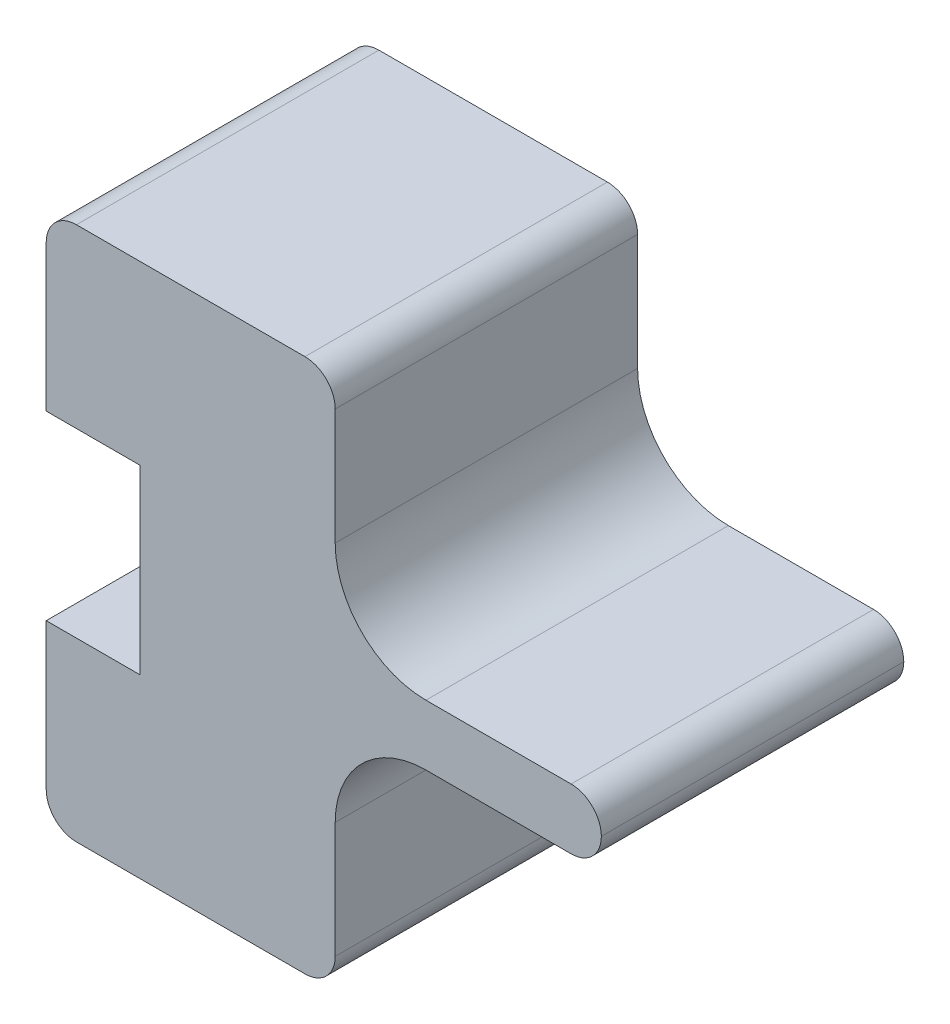
SolidWorks part; units mm, degrees
ref_plane "Plan de face" through (0, 0, 0) normal (0, 0, 1) x (1, 0, 0)
ref_plane "Plan de dessus" through (0, 0, 0) normal (0, 1, 0) x (1, 0, 0)
ref_plane "Plan de droite" through (0, 0, 0) normal (1, 0, 0) x (0, 0, -1)
sketch "Esquisse1" plane through (0, 0, 0) normal (0, 0, 1) x (1, 0, 0)
  line L0 (90, -10) -> (90, 10)
  line L1 (90, -58) -> (90, 58) construction
  line L2 (90, 10) -> (31.9949, 10)
  line L3 (1.9949, 40) -> (1.9949, 88.3751)
  line L4 (1.9949, 88.3751) -> (-83.5559, 88.3751)
  line L5 (-93.5559, 78.3751) -> (-93.5559, 30)
  line L6 (-93.5559, 30) -> (-22.5559, 30)
  line L7 (-22.5559, 30) -> (-22.5559, -30)
  line L8 (-73.7109, 0) -> (58.7084, 0) construction
  line L9 (-93.5559, -30) -> (-22.5559, -30)
  line L10 (-93.5559, -78.3751) -> (-93.5559, -30)
  line L11 (1.9949, -88.3751) -> (-83.5559, -88.3751)
  line L12 (1.9949, -40) -> (1.9949, -88.3751)
  line L13 (90, -10) -> (31.9949, -10)
  arc A0 (31.9949, 10) -> (1.9949, 40) centre (31.9949, 40) cw
  arc A1 (1.9949, -40) -> (31.9949, -10) centre (31.9949, -40) cw
  arc A2 (-93.5559, -78.3751) -> (-83.5559, -88.3751) centre (-83.5559, -78.3751) ccw
  arc A3 (-83.5559, 88.3751) -> (-93.5559, 78.3751) centre (-83.5559, 78.3751) ccw
  point P14 (-22.5559, 0)
  point P19 (90, 0)
  point P21 (1.9949, 10)
  point P24 (1.9949, -10)
  point P27 (-93.5559, -88.3751)
  point P30 (-93.5559, 88.3751)
  dimension "D6" = 30
  dimension "D7" = 30
  dimension "D8" = 10
  dimension "D1" = 30
  dimension "D2" = 71
  dimension "D3" = 22.5559
  dimension "D4" = 88.3751
  dimension "D5" = 10
extrude "Boss.-Extru.1" add sketch "Esquisse1" along normal blind 100
sketch "Esquisse2" plane through (-22.5559, 0, 0) normal (-1, 0, 0) x (0, 0, 1)
  line L1 (80, -30) -> (100, -30)
  line L2 (80, -30) -> (80, 30)
  line L3 (80, 30) -> (100, 30)
  line L4 (100, -30) -> (100, 30)
  line L5 (80, -30) -> (100, 30) construction
  line L6 (80, 30) -> (100, -30) construction
  point P0 (90, 0)
  dimension "D1" = 20
extrude "Boss.-Extru.2" add sketch "Esquisse2" along normal blind 40
fillet "Congé1" radius 10 1 edges at (1.9949, -88.3751, 50)
fillet "Congé2" radius 10 1 edges at (1.9949, 88.3751, 50)
fillet "Congé3" radius 10 2 edges at (90, -10, 50) (90, 10, 50)
